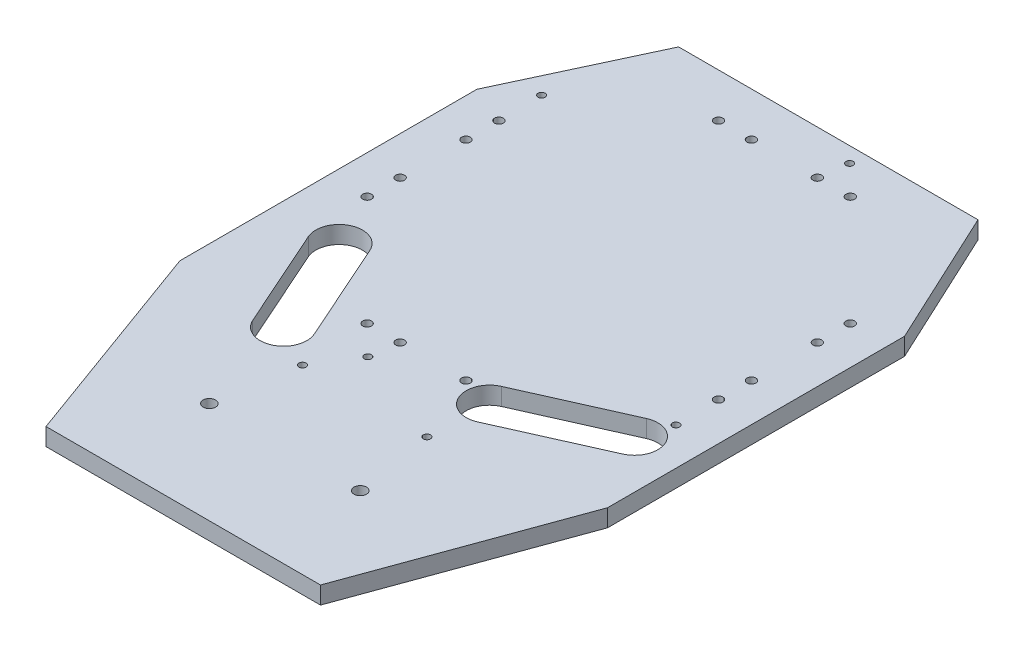
SolidWorks part; units mm, degrees
material "Pin"
ref_plane "Plan de face" through (0, 0, 0) normal (0, 0, 1) x (1, 0, 0)
ref_plane "Plan de dessus" through (0, 0, 0) normal (0, 1, 0) x (1, 0, 0)
ref_plane "Plan de droite" through (0, 0, 0) normal (1, 0, 0) x (0, 0, -1)
sketch "Esquisse3" plane through (0, 0, 0) normal (0, 1, 0) x (1, 0, 0)
  line L0 (-54.5332, 80) -> (54.5332, 80)
  line L1 (-77.9068, 29.8751) -> (-77.9068, -78.3266)
  line L2 (-77.9068, -78.3266) -> (-50, -155)
  line L3 (-50, -155) -> (50, -155)
  line L5 (77.9068, -78.3266) -> (77.9068, 29.8751)
  line L6 (50, -155) -> (77.9068, -78.3266)
  line L7 (-54.5332, 80) -> (-77.9068, 29.8751)
  line L8 (54.5332, 80) -> (77.9068, 29.8751)
  point P0 (-77.9068, 29.8751)
  point P2 (0, 80)
  point P7 (0, -155)
  dimension "D1" = 155
  dimension "D2" = 80
  dimension "D3" = 25
  dimension "D4" = 70
  dimension "D5" = 100
sketch "TB_boltPattern" plane through (0, 0, 0) normal (0, 1, 0) x (1, 0, 0)
  line L0 (0, 143.3581) -> (0, -141.7362) construction
  line L1 (-23, 57.7) -> (-13, 57.7) construction
  line L2 (-23, 57.7) -> (-23, 43.7) construction
  line L3 (-23, 43.7) -> (-13, 43.7) construction
  line L4 (-13, 57.7) -> (-13, 43.7) construction
  line L5 (-57.7, 23) -> (-43.7, 23) construction
  line L6 (-57.7, 23) -> (-57.7, 13) construction
  line L7 (-57.7, 13) -> (-43.7, 13) construction
  line L8 (-43.7, 23) -> (-43.7, 13) construction
  line L9 (-204.4729, 0) -> (279.6048, 0) construction
  circle A0 centre (-24, 64) radius 1.6 construction
  circle A1 centre (-12, 64) radius 1.6 construction
  circle A2 centre (-64, 24) radius 1.6 construction
  circle A3 centre (-64, 12) radius 1.6 construction
  point P8 (-18, 57.7)
  dimension "D5" = 3.2
  dimension "D10" = 6.3
  dimension "D1" = 12
  dimension "D2" = 12
  dimension "D3" = 40
  dimension "D4" = 40
  dimension "D6" = 14
  dimension "D7" = 10
  dimension "D8" = 1
  dimension "D9" = 6.3
  dimension "D11" = 1
  dimension "D12" = 12
  dimension "D13" = 12
sketch "HB_Footprint" plane through (0, 0, 0) normal (0, 1, 0) x (1, 0, 0)
  line L0 (13.3793, 74.3875) -> (64.2603, -39.7884) construction
  line L1 (64.2603, -39.7884) -> (-13.3793, -74.3875) construction
  line L2 (13.3793, 74.3875) -> (-64.2603, 39.7884) construction
  line L3 (-64.2603, 39.7884) -> (-13.3793, -74.3875) construction
  line L8 (29.8751, 77.9068) -> (-77.9068, 29.8751) construction
  line L9 (-77.9068, 29.8751) -> (-29.8751, -77.9068) construction
  line L10 (-29.8751, -77.9068) -> (77.9068, -29.8751) construction
  line L11 (29.8751, 77.9068) -> (77.9068, -29.8751) construction
  line L12 (53.891, 24.0158) -> (-53.891, -24.0158) construction
  line L13 (-25.4405, 57.0879) -> (0, 0) construction
  circle A0 centre (13.3793, 74.3875) radius 1.6 construction
  circle A1 centre (64.2603, -39.7884) radius 1.6 construction
  circle A2 centre (-64.2603, 39.7884) radius 1.6 construction
  circle A3 centre (-13.3793, -74.3875) radius 1.6 construction
  point P10 (-53.891, -24.0158)
  point P17 (77.9068, -29.8751)
  point P19 (38.8198, 17.2996)
  dimension "D4" = 3.2
  dimension "D1" = 125
  dimension "D2" = 85
  dimension "D3" = 118
extrude "Plate" add sketch "Esquisse3" against normal blind 6.35
ref_axis "Axe1" through (0, 0, 0) along (0, 1, 0)
hole_wizard "Dégagement M32" positions "Esquisse9" profile "Esquisse10" hole size "M3" standard "Ansi Metric"
sketch "Esquisse9" plane through (0, 0, 0) normal (0, 1, 0) x (1, 0, 0)
  point P0 (-24, 64)
  point P3 (-12, 64)
  point P6 (-64, 24)
  point P9 (-64, 12)
sketch "Esquisse10" plane through (-24, 0, -64) normal (1, 0, 0) x (0, 0, 1)
  line L0 (0, 0) -> (0, 7.3114)
  line L1 (0, 7.3114) -> (1.6, 6.35)
  line L2 (1.6, 6.35) -> (1.6, 0)
  line L5 (1.6, 0) -> (0, 0)
  line L10 (0, 7.3114) -> (-1.6, 6.35) construction
  line L11 (0, -6.35) -> (0, 107.95) construction
  dimension "Diamètre du perçage" = 3.2
  dimension "Profondeur du perçage" = 6.35
  dimension "Angle de pointe" = 118
pattern_circular "Répétition circulaire2" count 4 over 360 about axis through (0, 0, 0) along (0, 1, 0) of "Dégagement M32"
hole_wizard "Dégagement M33" positions "Esquisse11" profile "Esquisse12" hole size "M3" standard "Ansi Metric"
sketch "Esquisse11" plane through (0, 0, 0) normal (0, 1, 0) x (1, 0, 0)
  point P0 (13.3793, 74.3875)
  point P3 (-64.2603, 39.7884)
  point P6 (-13.3793, -74.3875)
  point P9 (64.2603, -39.7884)
sketch "Esquisse12" plane through (13.3793, 0, -74.3875) normal (1, 0, 0) x (0, 0, 1)
  line L0 (0, 0) -> (0, 7.1311)
  line L1 (0, 7.1311) -> (1.3, 6.35)
  line L2 (1.3, 6.35) -> (1.3, 0)
  line L5 (1.3, 0) -> (0, 0)
  line L10 (0, 7.1311) -> (-1.3, 6.35) construction
  line L11 (0, -6.35) -> (0, 107.95) construction
  dimension "Diamètre du perçage" = 2.6
  dimension "Profondeur du perçage" = 6.35
  dimension "Angle de pointe" = 118
sketch "Esquisse15" plane through (0, 0, 0) normal (0, 1, 0) x (1, 0, 0)
  line L0 (-27.48, -118) -> (27.48, -118) construction
  line L1 (0, 200143.3581) -> (0, -200141.7362) construction
  line L2 (-50, -155) -> (50, -155) construction
  circle A0 centre (-27.48, -118) radius 3.5746 construction
  circle A1 centre (27.48, -118) radius 3.5746 construction
  point P4 (0, -118)
  dimension "D1" = 54.96
  dimension "D2" = 37
hole_wizard "Dégagement M51" positions "Esquisse16" profile "Esquisse17" hole size "M5" standard "Ansi Metric"
sketch "Esquisse16" plane through (0, 0, 0) normal (0, 1, 0) x (1, 0, 0)
  point P0 (-27.48, -118)
  point P3 (27.48, -118)
sketch "Esquisse17" plane through (-27.48, 0, 118) normal (1, 0, 0) x (0, 0, 1)
  line L0 (0, 0) -> (0, 7.714)
  line L1 (0, 7.714) -> (2.27, 6.35)
  line L2 (2.27, 6.35) -> (2.27, 0)
  line L5 (2.27, 0) -> (0, 0)
  line L10 (0, 7.714) -> (-2.27, 6.35) construction
  line L11 (0, -6.35) -> (0, 107.95) construction
  dimension "Diamètre du perçage" = 4.54
  dimension "Profondeur du perçage" = 6.35
  dimension "Angle de pointe" = 118
sketch "puckFootprint" plane through (0, 0, 0) normal (0, 1, 0) x (1, 0, 0)
  line L0 (22.655, -88.8992) -> (-22.655, -88.8992) construction
  line L1 (30.89, -177.5892) -> (-30.89, -177.5892) construction
  line L2 (0, -88.8992) -> (0, -177.5892) construction
  line L3 (-50, -155) -> (50, -155) construction
  line L4 (0, -88.8992) -> (0, -73.8992) construction
  line L5 (0, 200143.3581) -> (0, -200141.7362) construction
  line L7 (64.2603, -39.7884) -> (-13.3793, -74.3875) construction
  circle A1 centre (-22.655, -88.8992) radius 1.5 construction
  circle A2 centre (22.655, -88.8992) radius 1.5 construction
  circle A3 centre (-30.89, -177.5892) radius 1.5 construction
  circle A4 centre (30.89, -177.5892) radius 1.5 construction
  point P8 (0, -125.2792)
  point P11 (0, -154.8992)
  point P12 (0, -141.4461)
  point P18 (0, -155)
  dimension "D4" = 3
  dimension "D1" = 36.38
  dimension "D2" = 45.31
  dimension "D3" = 52.31
  dimension "D5" = 61.78
  dimension "D6" = 15
  dimension "D7" = 5
  dimension "D8" = 81
hole_wizard "BoltPatternPuck" positions "Esquisse3D1" profile "Esquisse18" hole size "M3" standard "Ansi Metric"
sketch3d "Esquisse3D1"
  point P2 (-22.655, 0, 88.8992)
  point P5 (22.655, 0, 88.8992)
  point P9 (0, 0, 0)
sketch "Esquisse18" plane through (-22.655, 0, 88.8992) normal (1, 0, 0) x (0, 0, 1)
  line L0 (0, 0) -> (0, 7.1311)
  line L1 (0, 7.1311) -> (1.3, 6.35)
  line L2 (1.3, 6.35) -> (1.3, 0)
  line L5 (1.3, 0) -> (0, 0)
  line L10 (0, 7.1311) -> (-1.3, 6.35) construction
  line L11 (0, -6.35) -> (0, 107.95) construction
  dimension "Diamètre du perçage" = 2.6
  dimension "Profondeur du perçage" = 6.35
  dimension "Angle de pointe" = 118
sketch "Esquisse19" plane through (0, 0, 0) normal (0, 1, 0) x (1, 0, 0)
  line L0 (23.7319, -67.1552) -> (60.2681, -50.8732) construction
  line L1 (20.272, -59.3912) -> (56.8082, -43.1093)
  line L2 (27.1918, -74.9191) -> (63.728, -58.6372)
  line L3 (64.2603, -39.7884) -> (-13.3793, -74.3875) construction
  line L4 (-54.3522, -43.8629) -> (-38.0703, -80.3992) construction
  line L5 (-46.5883, -40.403) -> (-30.3063, -76.9393)
  line L6 (-62.1162, -47.3228) -> (-45.8342, -83.8591)
  line L7 (-77.9068, 29.8751) -> (-29.8751, -77.9068) construction
  line L8 (22.655, -88.8992) -> (-22.655, -88.8992) construction
  arc A0 (20.272, -59.3912) -> (27.1918, -74.9191) centre (23.7319, -67.1552) ccw
  arc A1 (63.728, -58.6372) -> (56.8082, -43.1093) centre (60.2681, -50.8732) ccw
  circle A2 centre (12, -64) radius 1.6 construction
  arc A3 (-46.5883, -40.403) -> (-62.1162, -47.3228) centre (-54.3522, -43.8629) ccw
  arc A4 (-45.8342, -83.8591) -> (-30.3063, -76.9393) centre (-38.0703, -80.3992) ccw
  point P2 (42, -59.0142)
  point P15 (-46.2113, -62.131)
  dimension "D5" = 8.5
  dimension "D1" = 17
  dimension "D2" = 40
  dimension "D3" = 30
  dimension "D4" = 40
extrude "Enlèv. mat.-Extru.1" cut sketch "Esquisse19" along direction (0, 1, 0) on the side against the normal up to next (6.35 mm away)
